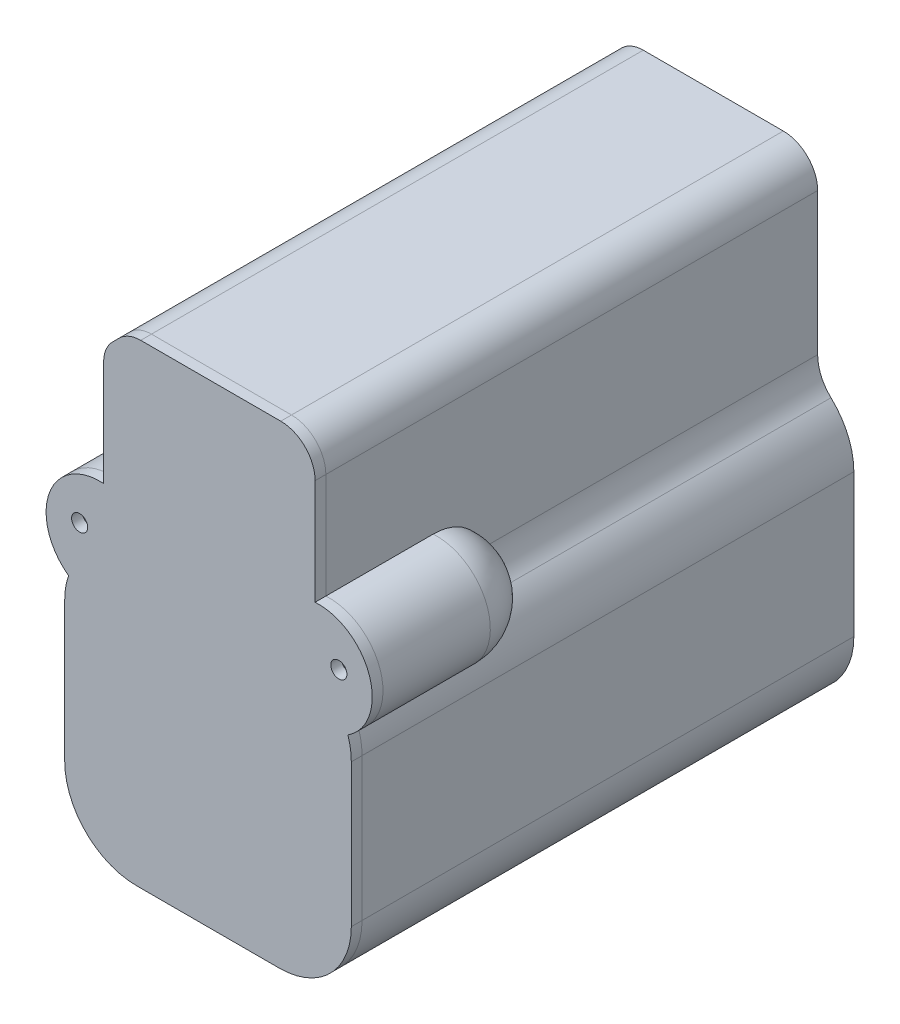
SolidWorks part; units mm, degrees
ref_plane "Front Plane" through (0, 0, 0) normal (0, 0, 1) x (1, 0, 0)
ref_plane "Top Plane" through (0, 0, 0) normal (0, 1, 0) x (1, 0, 0)
ref_plane "Right Plane" through (0, 0, 0) normal (1, 0, 0) x (0, 0, -1)
sketch "Sketch1" plane through (0, 0, 0) normal (0, 0, 1) x (1, 0, 0)
  line L1 (35, -50) -> (-35, -50)
  line L2 (35, -50) -> (35, 50)
  line L3 (35, 50) -> (-35, 50)
  line L4 (-35, -50) -> (-35, 50)
  line L5 (35, -50) -> (-35, 50) construction
  line L6 (35, 50) -> (-35, -50) construction
  point P0 (0, 0)
  dimension "D1" = 70
  dimension "D2" = 100
extrude "Boss-Extrude1" add sketch "Sketch1" along normal blind 2
sketch "Sketch2" plane through (0, 0, 0) normal (0, 0, -1) x (-1, 0, 0)
  line L0 (-17.2536, 39.8) -> (-17.2536, 13.2) construction
  line L1 (-13.0536, 9) -> (13.5464, 9) construction
  line L2 (17.7464, 13.2) -> (17.7464, 39.293) construction
  line L3 (16.7213, 41.7677) -> (15.5141, 42.9749) construction
  line L4 (13.0394, 44) -> (-13.0536, 44) construction
  line L5 (-17.2536, 39.8) -> (-17.2536, 13.3092) construction
  line L6 (-13.0536, 9) -> (13.5464, 9)
  line L7 (17.7464, 12.9384) -> (17.7464, 39.293) construction
  line L8 (16.7213, 41.7677) -> (15.5141, 42.9749) construction
  line L9 (13.0394, 44) -> (-13.0536, 44) construction
  line L10 (-24, -2.2) -> (-24, -28.8) construction
  line L11 (-12.8, -40) -> (13.8, -40) construction
  line L12 (25, -28.8) -> (25, -2.707) construction
  line L13 (21.9246, 4.7175) -> (20.7175, 5.9247) construction
  line L14 (13.2928, 9) -> (-12.8, 9) construction
  line L15 (-24, -2.2) -> (-24, -28.8) construction
  line L16 (-12.8, -40) -> (13.8, -40) construction
  line L17 (25, -28.8) -> (25, -2.707) construction
  line L18 (21.9246, 4.7175) -> (20.7175, 5.9247)
  line L19 (13.2928, 9) -> (-12.8, 9)
  line L20 (-17.4536, 39.8) -> (-17.4536, 13.3092)
  line L21 (13.0394, 44.2) -> (-13.0536, 44.2)
  line L22 (16.8627, 41.9092) -> (15.6556, 43.1163)
  line L23 (17.9464, 12.9384) -> (17.9464, 39.293)
  line L24 (25.2, -28.8) -> (25.2, -2.707)
  line L25 (-12.8, -40.2) -> (13.8, -40.2)
  line L26 (-24.2, -2.2) -> (-24.2, -28.8)
  line L27 (-26.2, -2.2) -> (-26.2, -28.8)
  line L28 (-12.8, -42.2) -> (13.8, -42.2)
  line L29 (27.2, -28.8) -> (27.2, -2.707)
  line L30 (19.9464, 12.9384) -> (19.9464, 39.293)
  line L31 (18.2769, 43.3234) -> (17.0698, 44.5306)
  line L32 (13.0393, 46.2) -> (-13.0536, 46.2)
  line L33 (-19.4536, 39.8) -> (-19.4536, 13.3092)
  arc A0 (-13.0536, 44) -> (-17.2536, 39.8) centre (-13.0536, 39.8) ccw construction
  arc A1 (-17.2536, 13.2) -> (-13.0536, 9) centre (-13.0536, 13.2) ccw construction
  arc A2 (13.5464, 9) -> (17.7464, 13.2) centre (13.5464, 13.2) ccw construction
  arc A3 (17.7464, 39.293) -> (16.7213, 41.7677) centre (14.2466, 39.293) ccw construction
  arc A4 (15.5141, 42.9749) -> (13.0394, 44) centre (13.0394, 40.5002) ccw construction
  arc A5 (-13.0536, 44) -> (-17.2536, 39.8) centre (-13.0536, 39.8) ccw construction
  arc A6 (-17.2536, 13.2) -> (-13.0536, 9) centre (-13.0536, 13.2) ccw
  arc A7 (13.5464, 9) -> (17.7464, 13.2) centre (13.5464, 13.2) ccw
  arc A8 (17.7464, 39.293) -> (16.7213, 41.7677) centre (14.2466, 39.293) ccw construction
  arc A9 (15.5141, 42.9749) -> (13.0394, 44) centre (13.0394, 40.5002) ccw construction
  arc A10 (-24, -28.8) -> (-12.8, -40) centre (-12.8, -28.8) ccw construction
  arc A11 (13.8, -40) -> (25, -28.8) centre (13.8, -28.8) ccw construction
  arc A12 (25, -2.707) -> (21.9246, 4.7175) centre (14.5002, -2.707) ccw construction
  arc A13 (20.7175, 5.9247) -> (13.2928, 9) centre (13.293, -1.4998) ccw construction
  arc A14 (-12.8, 9) -> (-24, -2.2) centre (-12.8, -2.2) ccw construction
  arc A15 (-24, -28.8) -> (-12.8, -40) centre (-12.8, -28.8) ccw construction
  arc A16 (13.8, -40) -> (25, -28.8) centre (13.8, -28.8) ccw construction
  arc A17 (25, -2.707) -> (21.2848, 5.3064) centre (14.5002, -2.707) ccw construction
  arc A18 (20.7175, 5.9247) -> (13.2928, 9) centre (13.293, -1.4998) ccw
  arc A19 (-20.4359, 5.9935) -> (-24, -2.2) centre (-12.8, -2.2) ccw construction
  arc A20 (21.2848, 5.3064) -> (17.7464, 12.9384) centre (27.7464, 12.9384) cw construction
  arc A21 (-20.4359, 5.9935) -> (-17.2536, 13.3092) centre (-27.2536, 13.3092) ccw construction
  arc A22 (-20.5722, 6.1398) -> (-17.4536, 13.3092) centre (-27.2536, 13.3092) ccw
  arc A23 (-13.0536, 44.2) -> (-17.4536, 39.8) centre (-13.0536, 39.8) ccw
  arc A24 (15.6556, 43.1163) -> (13.0394, 44.2) centre (13.0394, 40.5002) ccw
  arc A25 (17.9464, 39.293) -> (16.8627, 41.9092) centre (14.2466, 39.293) ccw
  arc A26 (21.414, 5.4591) -> (17.9464, 12.9384) centre (27.7464, 12.9384) cw
  arc A27 (25.2, -2.707) -> (21.414, 5.4591) centre (14.5002, -2.707) ccw
  arc A28 (13.8, -40.2) -> (25.2, -28.8) centre (13.8, -28.8) ccw
  arc A29 (-24.2, -28.8) -> (-12.8, -40.2) centre (-12.8, -28.8) ccw
  arc A30 (-20.5722, 6.1398) -> (-24.2, -2.2) centre (-12.8, -2.2) ccw
  arc A31 (-21.9358, 7.603) -> (-26.2, -2.2) centre (-12.8, -2.2) ccw
  arc A32 (-26.2, -28.8) -> (-12.8, -42.2) centre (-12.8, -28.8) ccw
  arc A33 (13.8, -42.2) -> (27.2, -28.8) centre (13.8, -28.8) ccw
  arc A34 (27.2, -2.707) -> (22.7063, 6.9855) centre (14.5002, -2.707) ccw
  arc A35 (22.7063, 6.9855) -> (19.9464, 12.9384) centre (27.7464, 12.9384) cw
  arc A36 (19.9464, 39.293) -> (18.2769, 43.3234) centre (14.2466, 39.293) ccw
  arc A37 (17.0698, 44.5306) -> (13.0393, 46.2) centre (13.0394, 40.5002) ccw
  arc A38 (-13.0536, 46.2) -> (-19.4536, 39.8) centre (-13.0536, 39.8) ccw
  arc A39 (-21.9358, 7.603) -> (-19.4536, 13.3092) centre (-27.2536, 13.3092) ccw
  line M23 (35, -50) -> (35, 50)
  line M24 (35, 50) -> (-35, 50)
  line M25 (-35, 50) -> (-35, -50)
  line M26 (-35, -50) -> (35, -50)
  dimension "D1" = 10
  dimension "D2" = 0.2
  dimension "D3" = 2
extrude "Cut-Extrude1" cut sketch "Sketch2" against normal up to next contours A31 A39 L33 A38 L32 A37 L31 A36 L30 A35 A34 L29 A33 L28 A32 L27 M26 M23 M24 M25 region at (0, -48.7793, 0)
sketch "Sketch3" plane through (0, 0, 0) normal (0, 0, -1) x (-1, 0, 0)
  line L0 (-19.4536, 39.8) -> (-19.4536, 13.3092) construction
  line L1 (-26.2, -2.2) -> (-26.2, -28.8) construction
  line L2 (-12.8, -42.2) -> (13.8, -42.2) construction
  line L3 (27.2, -28.8) -> (27.2, -2.707) construction
  line L4 (19.9464, 12.9384) -> (19.9464, 39.293) construction
  line L5 (18.2769, 43.3234) -> (17.0698, 44.5306) construction
  line L6 (13.0393, 46.2) -> (-13.0536, 46.2) construction
  line L7 (-19.4536, 39.8) -> (-19.4536, 13.3092)
  line L8 (-26.2, -2.2) -> (-26.2, -28.8)
  line L9 (-12.8, -42.2) -> (13.8, -42.2)
  line L10 (27.2, -28.8) -> (27.2, -2.707)
  line L11 (19.9464, 12.9384) -> (19.9464, 39.293)
  line L12 (18.2769, 43.3234) -> (17.0698, 44.5306)
  line L13 (13.0393, 46.2) -> (-13.0536, 46.2)
  arc A0 (-13.0536, 46.2) -> (-19.4536, 39.8) centre (-13.0536, 39.8) ccw construction
  arc A1 (-21.9358, 7.603) -> (-19.4536, 13.3092) centre (-27.2536, 13.3092) ccw construction
  arc A2 (-21.9358, 7.603) -> (-26.2, -2.2) centre (-12.8, -2.2) ccw construction
  arc A3 (-26.2, -28.8) -> (-12.8, -42.2) centre (-12.8, -28.8) ccw construction
  arc A4 (13.8, -42.2) -> (27.2, -28.8) centre (13.8, -28.8) ccw construction
  arc A5 (27.2, -2.707) -> (22.7063, 6.9855) centre (14.5002, -2.707) ccw construction
  arc A6 (19.9464, 12.9384) -> (22.7063, 6.9855) centre (27.7464, 12.9384) ccw construction
  arc A7 (19.9464, 39.293) -> (18.2769, 43.3234) centre (14.2466, 39.293) ccw construction
  arc A8 (17.0698, 44.5306) -> (13.0393, 46.2) centre (13.0394, 40.5002) ccw construction
  arc A9 (-13.0536, 46.2) -> (-19.4536, 39.8) centre (-13.0536, 39.8) ccw
  arc A10 (-21.9358, 7.603) -> (-19.4536, 13.3092) centre (-27.2536, 13.3092) ccw
  arc A11 (-21.9358, 7.603) -> (-26.2, -2.2) centre (-12.8, -2.2) ccw
  arc A12 (-26.2, -28.8) -> (-12.8, -42.2) centre (-12.8, -28.8) ccw
  arc A13 (13.8, -42.2) -> (27.2, -28.8) centre (13.8, -28.8) ccw
  arc A14 (27.2, -2.707) -> (22.7063, 6.9855) centre (14.5002, -2.707) ccw
  arc A15 (19.9464, 12.9384) -> (22.7063, 6.9855) centre (27.7464, 12.9384) ccw
  arc A16 (19.9464, 39.293) -> (18.2769, 43.3234) centre (14.2466, 39.293) ccw
  arc A17 (17.0698, 44.5306) -> (13.0393, 46.2) centre (13.0394, 40.5002) ccw
extrude "Extrude-Thin1" add sketch "Sketch3" against normal offset from surface (91.6373 mm away) 1.2 thin offset beyond the face yes thin type one direction reverse wall 2
sketch "Sketch4" plane through (0, 0, 91.6373) normal (0, 0, 1) x (1, 0, 0)
  line L0 (-19.9464, 12.9384) -> (-19.9464, 39.293) construction
  line L1 (-19.9464, 19.6314) -> (-26.4771, 1.5165) construction
  line L2 (-20.67, 9.6576) -> (-30.0773, 13.0491) construction
  line L10 (13.0536, 46.2) -> (-13.0394, 46.2)
  line L11 (-17.0698, 44.5306) -> (-18.277, 43.3233)
  line L12 (-19.9464, 39.293) -> (-19.9464, 12.9384)
  line L13 (-27.2, -2.707) -> (-27.2, -28.8)
  line L14 (-13.8, -42.2) -> (12.8, -42.2)
  line L15 (26.2, -28.8) -> (26.2, -2.2)
  line L16 (19.4536, 13.3092) -> (19.4536, 39.8)
  line L19 (-19.9464, 19.6314) -> (-19.9464, 12.9384)
  arc A0 (-19.9464, 19.6314) -> (-26.4771, 1.5165) centre (-20.67, 9.6576) ccw
  arc A1 (-22.7063, 6.9855) -> (-19.9464, 12.9384) centre (-27.7464, 12.9384) ccw construction
  arc A2 (-22.7063, 6.9855) -> (-27.2, -2.707) centre (-14.5002, -2.707) ccw construction
  arc A14 (19.4536, 39.8) -> (13.0536, 46.2) centre (13.0536, 39.8) ccw
  arc A15 (-13.0394, 46.2) -> (-17.0698, 44.5306) centre (-13.0394, 40.5002) ccw
  arc A16 (-18.277, 43.3233) -> (-19.9464, 39.293) centre (-14.2466, 39.293) ccw
  arc A17 (-22.7063, 6.9855) -> (-19.9464, 12.9384) centre (-27.7464, 12.9384) ccw
  arc A18 (-22.7063, 6.9855) -> (-27.2, -2.707) centre (-14.5002, -2.707) ccw
  arc A19 (-27.2, -28.8) -> (-13.8, -42.2) centre (-13.8, -28.8) ccw
  arc A20 (12.8, -42.2) -> (26.2, -28.8) centre (12.8, -28.8) ccw
  arc A21 (26.2, -2.2) -> (21.9358, 7.603) centre (12.8, -2.2) ccw
  arc A22 (19.4536, 13.3092) -> (21.9358, 7.603) centre (27.2536, 13.3092) ccw
  arc A26 (-22.7063, 6.9855) -> (-19.9464, 12.9384) centre (-27.7464, 12.9384) ccw
  arc A27 (-22.7063, 6.9855) -> (-26.4771, 1.5165) centre (-14.5002, -2.707) ccw
  dimension "D1" = 10
  dimension "D2" = 0
extrude "Boss-Extrude2" add sketch "Sketch4" against normal blind 30
sketch "Sketch5" plane through (0, 0, 91.6373) normal (0, 0, 1) x (1, 0, 0)
  line L0 (-19.9464, 19.6314) -> (-26.4771, 1.5165) construction
  line L1 (-18.8555, 8.8164) -> (-29.981, 13.3051) construction
  arc A0 (-21.414, 5.4591) -> (-17.9464, 12.9384) centre (-27.7464, 12.9384) ccw construction
  arc A1 (-19.9464, 19.6314) -> (-26.4771, 1.5165) centre (-20.67, 9.6576) ccw construction
  circle A2 centre (-24.4183, 11.0607) radius 3
  point P12 (-23.2118, 10.574)
  point P15 (-24.4183, 11.0607)
  dimension "D1" = 6
extrude "Cut-Extrude2" cut sketch "Sketch5" against normal blind 23
fillet "Fillet1" radius 10 1 edges at (-30.0773, 13.0491, 61.6373)
sketch "Sketch6" plane through (0, 0, 91.6373) normal (0, 0, 1) x (1, 0, 0)
  line L0 (19.4536, 39.8) -> (19.4536, 13.3092) construction
  line L8 (-19.9464, 39.293) -> (-19.9464, 19.6314)
  line L9 (-27.2, -2.707) -> (-27.2, -28.8)
  line L10 (-13.8, -42.2) -> (12.8, -42.2)
  line L11 (26.2, -28.8) -> (26.2, -2.2)
  line L12 (19.4536, 13.3092) -> (19.4536, 39.8)
  line L13 (13.0536, 46.2) -> (-13.0394, 46.2)
  line L14 (-17.0698, 44.5306) -> (-18.277, 43.3233)
  line L19 (19.4536, 13.3092) -> (19.4536, 20.1768)
  arc A0 (19.4536, 20.1768) -> (25.5791, 1.8318) centre (20.101, 10.1978) cw
  arc A1 (19.4536, 13.3092) -> (21.9358, 7.603) centre (27.2536, 13.3092) ccw construction
  arc A2 (26.2, -2.2) -> (21.9358, 7.603) centre (12.8, -2.2) ccw construction
  arc A12 (-19.9464, 19.6314) -> (-26.4771, 1.5165) centre (-20.67, 9.6576) ccw
  arc A13 (-26.4771, 1.5165) -> (-27.2, -2.707) centre (-14.5002, -2.707) ccw
  arc A14 (-27.2, -28.8) -> (-13.8, -42.2) centre (-13.8, -28.8) ccw
  arc A15 (12.8, -42.2) -> (26.2, -28.8) centre (12.8, -28.8) ccw
  arc A16 (26.2, -2.2) -> (21.9358, 7.603) centre (12.8, -2.2) ccw
  arc A17 (19.4536, 13.3092) -> (21.9358, 7.603) centre (27.2536, 13.3092) ccw
  arc A18 (19.4536, 39.8) -> (13.0536, 46.2) centre (13.0536, 39.8) ccw
  arc A19 (-13.0394, 46.2) -> (-17.0698, 44.5306) centre (-13.0394, 40.5002) ccw
  arc A20 (-18.277, 43.3233) -> (-19.9464, 39.293) centre (-14.2466, 39.293) ccw
  arc A25 (25.5791, 1.8318) -> (21.9358, 7.603) centre (12.8, -2.2) ccw
  arc A26 (19.4536, 13.3092) -> (21.9358, 7.603) centre (27.2536, 13.3092) ccw
  dimension "D1" = 10
  dimension "D2" = 0
extrude "Boss-Extrude3" add sketch "Sketch6" against normal blind 30
fillet "Fillet3" radius 10 1 edges at (29.5862, 13.365, 61.6373)
sketch "Sketch7" plane through (0, 0, 91.6373) normal (0, 0, 1) x (1, 0, 0)
  line L0 (19.4536, 20.1768) -> (25.5791, 1.8318) construction
  line L1 (18.267, 9.4) -> (29.4908, 13.6374) construction
  arc A0 (17.4536, 13.3092) -> (20.5722, 6.1398) centre (27.2536, 13.3092) ccw construction
  arc A1 (25.5791, 1.8318) -> (19.4536, 20.1768) centre (20.101, 10.1978) ccw construction
  circle A2 centre (23.8789, 11.5187) radius 3
  point P12 (22.5163, 11.0043)
  point P16 (23.8789, 11.5187)
  dimension "D1" = 6
extrude "Cut-Extrude3" cut sketch "Sketch7" against normal blind 23
sketch "Sketch9" plane through (0, 0, 0) normal (0, 0, -1) x (-1, 0, 0)
  line L28 (13.7464, 15) -> (13.7464, 38)
  line L29 (11.7464, 40) -> (-11.2536, 40)
  line L30 (-13.2536, 38) -> (-13.2536, 15)
  line L31 (-11.2536, 13) -> (11.7464, 13)
  line L32 (13.7464, 15) -> (13.7464, 38)
  line L33 (11.7464, 40) -> (-11.2536, 40)
  line L34 (-13.2536, 38) -> (-13.2536, 15)
  line L35 (-11.2536, 13) -> (11.7464, 13)
  line L52 (-12.8, -36) -> (13.8, -36)
  line L53 (21, -28.8) -> (21, -2.707)
  line L54 (19.0962, 1.8891) -> (17.889, 3.0962)
  line L55 (13.2929, 5) -> (-12.8, 5)
  line L56 (-20, -2.2) -> (-20, -28.8)
  line L57 (-12.8, -36) -> (13.8, -36)
  line L58 (21, -28.8) -> (21, -2.707)
  line L59 (19.0962, 1.8891) -> (17.889, 3.0962)
  line L60 (13.2929, 5) -> (-12.8, 5)
  line L61 (-20, -2.2) -> (-20, -28.8)
  arc A28 (11.7464, 13) -> (13.7464, 15) centre (11.7464, 15) ccw
  arc A29 (13.7464, 38) -> (11.7464, 40) centre (11.7464, 38) ccw
  arc A30 (-11.2536, 40) -> (-13.2536, 38) centre (-11.2536, 38) ccw
  arc A31 (-13.2536, 15) -> (-11.2536, 13) centre (-11.2536, 15) ccw
  arc A32 (11.7464, 13) -> (13.7464, 15) centre (11.7464, 15) ccw
  arc A33 (13.7464, 38) -> (11.7464, 40) centre (11.7464, 38) ccw
  arc A34 (-11.2536, 40) -> (-13.2536, 38) centre (-11.2536, 38) ccw
  arc A35 (-13.2536, 15) -> (-11.2536, 13) centre (-11.2536, 15) ccw
  arc A52 (-20, -28.8) -> (-12.8, -36) centre (-12.8, -28.8) ccw
  arc A53 (13.8, -36) -> (21, -28.8) centre (13.8, -28.8) ccw
  arc A54 (21, -2.707) -> (19.0962, 1.8891) centre (14.5002, -2.707) ccw
  arc A55 (17.889, 3.0962) -> (13.2929, 5) centre (13.293, -1.4998) ccw
  arc A56 (-12.8, 5) -> (-20, -2.2) centre (-12.8, -2.2) ccw
  arc A57 (-20, -28.8) -> (-12.8, -36) centre (-12.8, -28.8) ccw
  arc A58 (13.8, -36) -> (21, -28.8) centre (13.8, -28.8) ccw
  arc A59 (21, -2.707) -> (19.0962, 1.8891) centre (14.5002, -2.707) ccw
  arc A60 (17.889, 3.0962) -> (13.2929, 5) centre (13.293, -1.4998) ccw
  arc A61 (-12.8, 5) -> (-20, -2.2) centre (-12.8, -2.2) ccw
  dimension "D1" = 1
  dimension "D2" = 1
extrude "Cut-Extrude4" cut sketch "Sketch9" against normal up to next
sketch "Sketch10" plane through (0, 0, 91.6373) normal (0, 0, 1) x (1, 0, 0)
  line L0 (26.2, -2.2) -> (26.2, -28.8) construction
  line L1 (12.8, -42.2) -> (-13.8, -42.2) construction
  line L2 (-27.2, -28.8) -> (-27.2, -2.707) construction
  line L3 (19.4536, 39.8) -> (19.4536, 20.1768) construction
  line L4 (-13.0393, 46.2) -> (13.0536, 46.2) construction
  line L5 (-18.2769, 43.3234) -> (-17.0698, 44.5306) construction
  line L6 (-19.9464, 19.6314) -> (-19.9464, 39.293) construction
  line L7 (26.2, -2.2) -> (26.2, -28.8)
  line L8 (12.8, -42.2) -> (-13.8, -42.2)
  line L9 (-27.2, -28.8) -> (-27.2, -2.707)
  line L10 (19.4536, 39.8) -> (19.4536, 20.1768)
  line L11 (-13.0393, 46.2) -> (13.0536, 46.2)
  line L12 (-18.2769, 43.3234) -> (-17.0698, 44.5306)
  line L13 (-19.9464, 19.6314) -> (-19.9464, 39.293)
  arc A0 (-26.4771, 1.5165) -> (-27.2, -2.707) centre (-14.5002, -2.707) ccw construction
  arc A1 (26.2, -2.2) -> (25.5791, 1.8318) centre (12.8, -2.2) ccw construction
  arc A2 (12.8, -42.2) -> (26.2, -28.8) centre (12.8, -28.8) ccw construction
  arc A3 (-27.2, -28.8) -> (-13.8, -42.2) centre (-13.8, -28.8) ccw construction
  arc A4 (25.5791, 1.8318) -> (19.4536, 20.1768) centre (20.101, 10.1978) ccw construction
  arc A5 (-19.9464, 19.6314) -> (-26.4771, 1.5165) centre (-20.67, 9.6576) ccw construction
  arc A6 (19.4536, 39.8) -> (13.0536, 46.2) centre (13.0536, 39.8) ccw construction
  arc A7 (-13.0393, 46.2) -> (-17.0698, 44.5306) centre (-13.0394, 40.5002) ccw construction
  arc A8 (-18.2769, 43.3234) -> (-19.9464, 39.293) centre (-14.2466, 39.293) ccw construction
  arc A9 (-26.4771, 1.5165) -> (-27.2, -2.707) centre (-14.5002, -2.707) ccw
  arc A10 (26.2, -2.2) -> (25.5791, 1.8318) centre (12.8, -2.2) ccw
  arc A11 (12.8, -42.2) -> (26.2, -28.8) centre (12.8, -28.8) ccw
  arc A12 (-27.2, -28.8) -> (-13.8, -42.2) centre (-13.8, -28.8) ccw
  arc A13 (25.5791, 1.8318) -> (19.4536, 20.1768) centre (20.101, 10.1978) ccw
  arc A14 (-19.9464, 19.6314) -> (-26.4771, 1.5165) centre (-20.67, 9.6576) ccw
  arc A15 (19.4536, 39.8) -> (13.0536, 46.2) centre (13.0536, 39.8) ccw
  arc A16 (-13.0393, 46.2) -> (-17.0698, 44.5306) centre (-13.0394, 40.5002) ccw
  arc A17 (-18.2769, 43.3234) -> (-19.9464, 39.293) centre (-14.2466, 39.293) ccw
extrude "Boss-Extrude4" add sketch "Sketch10" along normal blind 2 separate body
sketch "Sketch11" plane through (0, 0, 93.6373) normal (0, 0, 1) x (1, 0, 0)
  circle A0 centre (-24.4183, 11.0607) radius 1.5
  circle A1 centre (23.8789, 11.5187) radius 1.5
  dimension "D1" = 3
  dimension "D2" = 3
extrude "Cut-Extrude5" cut sketch "Sketch11" against normal up to next (2 mm away)
sketch "Sketch12" plane through (-19.9464, 0, 0) normal (-1, 0, 0) x (0, 0, 1)
  line L0 (30.2675, 17.7465) -> (39.2675, 17.7465) construction
  line L1 (39.2675, 17.7465) -> (39.2675, 34.7465) construction
  line L2 (39.2675, 34.7465) -> (30.2675, 34.7465) construction
  line L3 (30.2675, 34.7465) -> (30.2675, 17.7465) construction
  line L4 (30.2675, 17.7465) -> (39.2675, 17.7465) construction
  line L5 (39.2675, 17.7465) -> (39.2675, 34.7465) construction
  line L6 (39.2675, 34.7465) -> (30.2675, 34.7465) construction
  line L7 (30.2675, 34.7465) -> (30.2675, 17.7465) construction
  line L8 (30.2675, 16.7465) -> (39.2675, 16.7465)
  line L9 (40.2675, 17.7465) -> (40.2675, 34.7465)
  line L10 (39.2675, 35.7465) -> (30.2675, 35.7465)
  line L11 (29.2675, 34.7465) -> (29.2675, 17.7465)
  line L12 (29.2675, 35.7465) -> (29.2675, 16.7465) construction
  line L13 (29.2675, 16.7465) -> (40.2675, 16.7465) construction
  line L14 (40.2675, 16.7465) -> (40.2675, 35.7465) construction
  line L15 (40.2675, 35.7465) -> (29.2675, 35.7465) construction
  arc A0 (29.2675, 17.7465) -> (30.2675, 16.7465) centre (30.2675, 17.7465) ccw
  arc A1 (40.2675, 17.7465) -> (39.2675, 16.7465) centre (39.2675, 17.7465) cw
  arc A2 (40.2675, 34.7465) -> (39.2675, 35.7465) centre (39.2675, 34.7465) ccw
  arc A3 (29.2675, 34.7465) -> (30.2675, 35.7465) centre (30.2675, 34.7465) cw
  dimension "D2" = 1
  dimension "D1" = 1
extrude "Cut-Extrude6" cut sketch "Sketch12" against normal up to next (2 mm away)
sketch "Sketch13" plane through (-27.2, 0, 0) normal (-1, 0, 0) x (0, 0, 1)
  line L0 (78.947, -24) -> (87.8341, -24) construction
  line L1 (87.8341, -24) -> (87.947, -7) construction
  line L2 (78.947, -7) -> (78.947, -24) construction
  line L3 (87.947, -7) -> (78.947, -7) construction
  line L4 (78.947, -24) -> (87.8341, -24) construction
  line L5 (87.8341, -24) -> (87.947, -7) construction
  line L6 (78.947, -7) -> (78.947, -24) construction
  line L7 (87.947, -7) -> (78.947, -7) construction
  line L8 (78.947, -25) -> (87.8341, -25)
  line L9 (88.8341, -24.0066) -> (88.9469, -7.0066)
  line L10 (87.947, -6) -> (78.947, -6)
  line L11 (77.947, -7) -> (77.947, -24)
  line L12 (77.947, -6) -> (77.947, -25) construction
  line L13 (77.947, -25) -> (88.8275, -25) construction
  line L14 (88.8275, -25) -> (88.9536, -6) construction
  line L15 (88.9536, -6) -> (77.947, -6) construction
  arc A0 (77.947, -24) -> (78.947, -25) centre (78.947, -24) ccw
  arc A1 (88.8341, -24.0066) -> (87.8341, -25) centre (87.8341, -24) cw
  arc A2 (88.9469, -7.0066) -> (87.947, -6) centre (87.947, -7) ccw
  arc A3 (77.947, -7) -> (78.947, -6) centre (78.947, -7) cw
  dimension "D2" = 1
  dimension "D1" = 1
extrude "Cut-Extrude7" cut sketch "Sketch13" against normal up to next (2 mm away)
equation "\"base_thickness\"= 2"
equation "\"front_thickness\"= 2"
equation "\"back_offset\"= 1.5"
equation "\"base_side_offset\"= 1"
equation "\"hole_inner_radius\"=2"
equation "\"snap_fit_thickness\"= 2"
equation "\"hole_outer_radius\"= 6"
equation "\"base_enclosure_camera_gap\"= 1"
equation "\"camera_front_enclosure_gap\"= 4"
equation "\"usb_hole_width\"= 9"
equation "\"usb_hole_length\"= 17"
equation "\"snap_fit_width\"= 6"
equation "\"snap_fit_base_length\"= 5.5"
equation "\"snap_fit_front_length\"= 7"
equation "\"snap_fit_height\"= 0.9"
equation "\"snap_fit_front_length_wide_cam\"= 8"
equation "\"D1@Boss-Extrude1\"=\"base_thickness\""
equation "\"outer_enclosure_offset\"= 0.2"
equation "\"D2@Sketch2\"=\"outer_enclosure_offset\""
equation "\"D3@Sketch2\"=\"base_thickness\""
equation "\"D5@Extrude-Thin1\"=\"base_thickness\""
equation "\"D1@Extrude-Thin1\"=\"outer_enclosure_offset\"+1"
equation "\"D1@Sketch5\"=\"hole_outer_radius\""
equation "\"D1@Sketch7\"=\"hole_outer_radius\""
equation "\"D1@Boss-Extrude4\"=\"base_thickness\""
